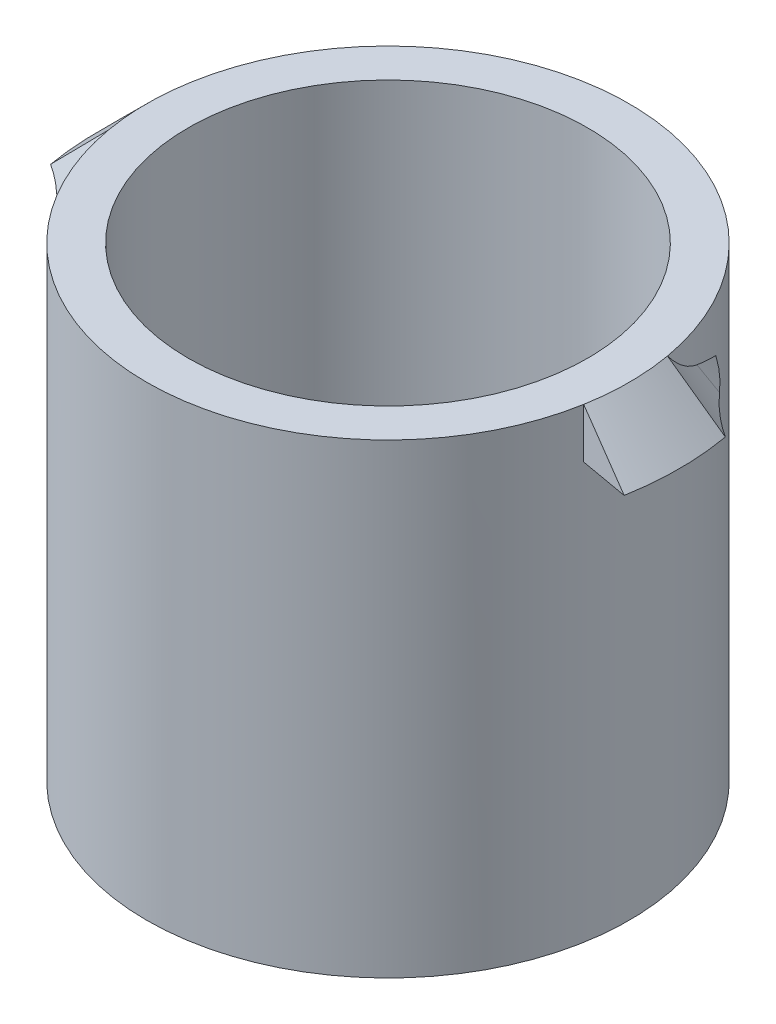
SolidWorks part; units mm, degrees
ref_plane "Alzado" through (0, 0, 0) normal (0, 0, 1) x (1, 0, 0)
ref_plane "Planta" through (0, 0, 0) normal (0, 1, 0) x (1, 0, 0)
ref_plane "Vista lateral" through (0, 0, 0) normal (1, 0, 0) x (0, 0, -1)
sketch "Croquis1" plane through (0, 0, 0) normal (0, 0, 1) x (1, 0, 0)
  line L0 (0, 15.9574) -> (0, -20.3191) construction
  line L1 (29.6768, 0) -> (-38.6211, 0) construction
  line L2 (-14.5, 12.5) -> (-12, 12.5)
  line L3 (-14.5, 12.5) -> (-14.5, -12.5)
  line L4 (-14.5, -12.5) -> (-12, -12.5)
  line L5 (-12, 12.5) -> (-12, -12.5)
  line L7 (-14.5, -12.5) -> (0, -12.5)
  line L8 (-14.5, -12.5) -> (-14.5, -15.5)
  line L9 (-14.5, -15.5) -> (0, -15.5)
  line L10 (0, -12.5) -> (0, -15.5)
  dimension "D1" = 25
  dimension "D2" = 2.5
  dimension "D3" = 12
  dimension "D4" = 3
revolve "Revolución1" add sketch "Croquis1" angle 360 about L0 region at (-13.25, 0, 0) region at (-7.25, -14, 0)
sketch "Croquis2" plane through (0, 0, 0) normal (0, 0, 1) x (1, 0, 0)
  line L0 (0, 15.7244) -> (0, -9.4926) construction
  line L1 (-14.5, 12.5) -> (-17.5, 9.5)
  line L2 (-14.5, 12.5) -> (-14.5, -15.5) construction
  line L3 (-17.5, 9.5) -> (-14.5, 9.5)
  line L4 (-14.5, 9.5) -> (-14.5, 12.5)
  line L5 (14.5, 12.5) -> (-14.5, 12.5) construction
  line L6 (17.5, 9.5) -> (14.5, 9.5)
  line L7 (14.5, 12.5) -> (17.5, 9.5)
  line L8 (14.5, 9.5) -> (14.5, 12.5)
  dimension "D1" = 3
  dimension "D2" = 3
  dimension "D3" = 17.5
revolve "Revolución2" add sketch "Croquis2" angle 20 mid plane about L0 region at (-15.5, 10.5, 0)
mirror "Simetría1" about plane through (0, 0, 0) normal (1, 0, 0) of "Revolución2"
sketch "Croquis3" plane through (0, 12.5, 0) normal (0, 1, 0) x (1, 0, 0)
  line L0 (-12.4097, -7.5) -> (-17.5, 0) construction
  line L1 (12.4097, 7.5) -> (-12.4097, 7.5) construction
  line L2 (12.4097, 7.5) -> (12.4097, -7.5) construction
  line L3 (12.4097, -7.5) -> (-12.4097, -7.5) construction
  line L4 (-12.4097, 7.5) -> (-12.4097, -7.5) construction
  line L5 (12.4097, 7.5) -> (-12.4097, -7.5) construction
  line L6 (12.4097, -7.5) -> (-12.4097, 7.5) construction
  arc A0 (-14.2797, -2.5179) -> (14.2797, -2.5179) centre (0, 0) ccw construction
  arc A1 (-17.2341, 3.0388) -> (-17.2341, -3.0388) centre (0, 0) ccw construction
  circle A2 centre (0, 0) radius 12 construction
  spline S0 degree 3 poles (-17.5, 0) (-16.5941, -5.1411) (-12.3684, -8.5687) (-7.6765, -9.2234) knots 0 0 0 0 1 1 1 1
  point P0 (0, 0)
  point P9 (-7.6765, -9.2234)
  dimension "D1" = 15
  dimension "D2" = 10.8788
  dimension "D3" = 8.3123
  dimension "D4" = 9.2234
sketch "Croquis4" plane through (0, 0, 0) normal (0, 0, 1) x (1, 0, 0)
  line L3 (-17.2341, 9.5) -> (-14.2797, 9.5)
  line L4 (-14.2797, 9.5) -> (-14.2797, 12.5)
  line L5 (-14.2797, 12.5) -> (-17.2341, 9.5)
  line L6 (-17.2341, 9.5) -> (-14.2797, 9.5)
  line L7 (-14.2797, 9.5) -> (-14.2797, 12.5)
  line L8 (-14.2797, 12.5) -> (-17.2341, 9.5)
  dimension "D1" = 0
sweep "Barrer3" add profiles "Croquis4" path "Croquis3"
fillet "Redondeo1" radius 10 1 edges at (-15.2861, 10.5071, 2.6954)
pattern_circular "MatrizC4" count 2 every 180 about axis through (0, 12.5, 0) along (0, 1, 0) of "Barrer3"
fillet "Redondeo2" radius 10 1 edges at (15.2861, 10.5071, -2.6954)
sketch "Croquis5" plane through (0, 12.5, 0) normal (0, 1, 0) x (1, 0, 0)
  circle A0 centre (0, 0) radius 12 construction
  circle A1 centre (0, 0) radius 12
extrude "Cortar-Extruir1" cut sketch "Croquis5" against normal blind 10
